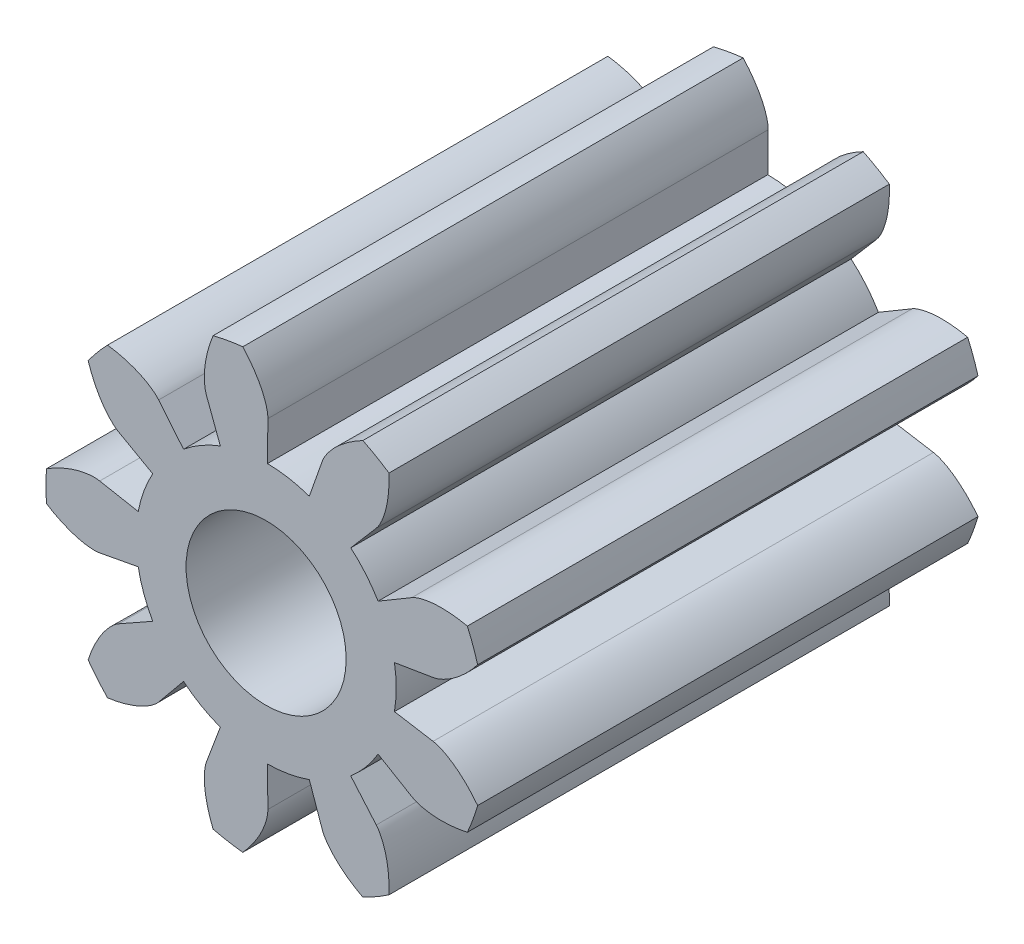
SolidWorks part; units mm, degrees
ref_plane "前视基准面" through (0, 0, 0) normal (0, 0, 1) x (1, 0, 0)
ref_plane "上视基准面" through (0, 0, 0) normal (0, 1, 0) x (1, 0, 0)
ref_plane "右视基准面" through (0, 0, 0) normal (1, 0, 0) x (0, 0, -1)
other "Configuration Table"
sketch "草图1" plane through (0, 0, 0) normal (0, 0, 1) x (1, 0, 0)
  line L0 (0, 0) -> (0.9, 0) construction
  line L1 (0, 0) -> (0.8863, 0.1563) construction
  line L2 (0, 0) -> (0.8344, 0.1381)
  line L3 (0.8863, 0.1563) -> (0.8863, -0.1563) construction
  line L4 (0, 0) -> (0.8344, -0.1381)
  circle A0 centre (0, 0) radius 1.1
  circle A1 centre (0, 0) radius 0.9 construction
  circle A2 centre (0, 0) radius 0.65
  circle A3 centre (0, 0) radius 0.8457 construction
  circle A4 centre (0, 0) radius 0.4
  spline S0 degree 4 poles (0.8344, 0.1381) (0.8407, 0.1391) (0.8583, 0.1434) (0.8902, 0.1567) (0.9385, 0.1852) (0.9947, 0.2314) (1.0578, 0.3003) (1.1187, 0.3914) (1.1706, 0.5) (1.2099, 0.6235) (1.2335, 0.7509) (1.2426, 0.8802) (1.238, 1.016) (1.2147, 1.1827) (1.1617, 1.3766) (1.0676, 1.5905) (0.9281, 1.8092) (0.7581, 2.0054) (0.5641, 2.1769) (0.3484, 2.322) (0.1192, 2.4402) (-0.1262, 2.5304) (-0.3732, 2.5938) (-0.6374, 2.6288) (-0.8395, 2.6375) (-1.0646, 2.6268) (-1.2145, 2.6094) (-1.3852, 2.5832) (-1.4515, 2.5634) (-1.518, 2.549) knots 0 0 0 0 0 0.005604 0.015718 0.02996 0.048734 0.068727 0.096889 0.125051 0.153212 0.181374 0.209535 0.237696 0.271429 0.327752 0.384075 0.440398 0.496721 0.553044 0.609367 0.66569 0.722013 0.778336 0.834659 0.890982 0.909091 0.954545 1 1 1 1 1 construction
  spline S1 degree 4 poles (0.8344, 0.1381) (0.8407, 0.1391) (0.8583, 0.1434) (0.8902, 0.1567) (0.9385, 0.1852) (0.9947, 0.2314) (1.0578, 0.3003) (1.1187, 0.3914) (1.1706, 0.5) (1.2099, 0.6235) (1.2335, 0.7509) (1.2426, 0.8802) (1.238, 1.016) (1.2147, 1.1827) (1.1617, 1.3766) (1.0676, 1.5905) (0.9281, 1.8092) (0.7581, 2.0054) (0.5641, 2.1769) (0.3484, 2.322) (0.1192, 2.4402) (-0.1262, 2.5304) (-0.3732, 2.5938) (-0.6374, 2.6288) (-0.8395, 2.6375) (-1.0065, 2.6296) (-1.0845, 2.623) (-1.1033, 2.6212) knots 0 0 0 0 0 0.005604 0.015718 0.02996 0.048734 0.068727 0.096889 0.125051 0.153212 0.181374 0.209535 0.237696 0.271429 0.327752 0.384075 0.440398 0.496721 0.553044 0.609367 0.66569 0.722013 0.778336 0.834659 0.890982 0.909091 0.909091 0.909091 0.909091 0.909091
  spline S2 degree 4 poles (0.8344, -0.1381) (0.8407, -0.1391) (0.8583, -0.1434) (0.8902, -0.1567) (0.9385, -0.1852) (0.9947, -0.2314) (1.0578, -0.3003) (1.1187, -0.3914) (1.1706, -0.5) (1.2099, -0.6235) (1.2335, -0.7509) (1.2426, -0.8802) (1.238, -1.016) (1.2147, -1.1827) (1.1617, -1.3766) (1.0676, -1.5905) (0.9281, -1.8092) (0.7581, -2.0054) (0.5641, -2.1769) (0.3484, -2.322) (0.1192, -2.4402) (-0.1262, -2.5304) (-0.3732, -2.5938) (-0.6374, -2.6288) (-0.8395, -2.6375) (-1.0646, -2.6268) (-1.2145, -2.6094) (-1.3852, -2.5832) (-1.4515, -2.5634) (-1.518, -2.549) knots 0 0 0 0 0 0.005604 0.015718 0.02996 0.048734 0.068727 0.096889 0.125051 0.153212 0.181374 0.209535 0.237696 0.271429 0.327752 0.384075 0.440398 0.496721 0.553044 0.609367 0.66569 0.722013 0.778336 0.834659 0.890982 0.909091 0.954545 1 1 1 1 1 construction
  spline S3 degree 4 poles (0.8344, -0.1381) (0.8407, -0.1391) (0.8583, -0.1434) (0.8902, -0.1567) (0.9385, -0.1852) (0.9947, -0.2314) (1.0578, -0.3003) (1.1187, -0.3914) (1.1706, -0.5) (1.2099, -0.6235) (1.2335, -0.7509) (1.2426, -0.8802) (1.238, -1.016) (1.2147, -1.1827) (1.1617, -1.3766) (1.0676, -1.5905) (0.9281, -1.8092) (0.7581, -2.0054) (0.5641, -2.1769) (0.3484, -2.322) (0.1192, -2.4402) (-0.1262, -2.5304) (-0.3732, -2.5938) (-0.6374, -2.6288) (-0.8395, -2.6375) (-1.0065, -2.6296) (-1.0845, -2.623) (-1.1033, -2.6212) knots 0 0 0 0 0 0.005604 0.015718 0.02996 0.048734 0.068727 0.096889 0.125051 0.153212 0.181374 0.209535 0.237696 0.271429 0.327752 0.384075 0.440398 0.496721 0.553044 0.609367 0.66569 0.722013 0.778336 0.834659 0.890982 0.909091 0.909091 0.909091 0.909091 0.909091
  point P15 (0.8863, 0)
  dimension "齿顶圆直径" = 2.2
  dimension "分度圆直径" = 1.8
  dimension "齿根圆直径" = 1.3
  dimension "基圆直径" = 1.6914
  dimension "内孔直径" = 0.8
  dimension "渐近线镜像线夹角" = 10
extrude "凸台-拉伸1" add sketch "草图1" along normal blind 2.5 contours A0 | A4
extrude "切除-拉伸1" cut sketch "草图1<3>" along normal through all contours A2 S3 A0 S1 region at (0.9092, 0, 0)
sketch "草图1<3>" plane through (0, 0, 0) normal (0, 0, 1) x (1, 0, 0) same geometry as "草图1"
pattern_circular "阵列(圆周)1" count 9 every 40 about axis through (0, 0, 2.5) along (0, 0, 1) of "切除-拉伸1"
equation "\"m\"= 0.2'模数"
equation "\"z\" = 9'齿数"
equation "\"a\"= 20度'压力角"
equation "\"d\"= \"m\" * \"z\"'分度圆直径"
equation "\"da\"= ( \"z\" + 2 ) * \"m\"'齿顶圆直径"
equation "\"df\"= ( \"z\" - 2.5 ) * \"m\"'齿根圆直径"
equation "\"s\"= 0.5 * PI * \"m\"'分度圆齿厚"
equation "\"r\"= 0.38 * \"m\"'齿根圆角"
equation "\"B\"= 0.3 * \"d\"'齿厚"
equation "\"db\"= \"m\" * \"z\" * cos ( \"a\" )'基圆直径"
equation "\"rb\"= \"db\" / 2'基圆半径"
equation "\"齿顶圆直径@草图1\"= \"da\""
equation "\"分度圆直径@草图1\"= \"d\""
equation "\"齿根圆直径@草图1\"= \"df\""
equation "\"基圆直径@草图1\"= \"db\""
equation "\"渐近线镜像线夹角@草图1\"= 360 / 4 / \"z\""
equation "\"h\" = 2.5'齿轮厚度"
equation "\"ir\"= 0.8'内孔直径"
equation "\"内孔直径@草图1\"= \"ir\""
equation "\"齿轮厚@凸台-拉伸1\"= \"h\""
equation "\"齿轮夹角@阵列(圆周)1\"= 360 / \"z\""
equation "\"齿数@阵列(圆周)1\"= \"z\""
